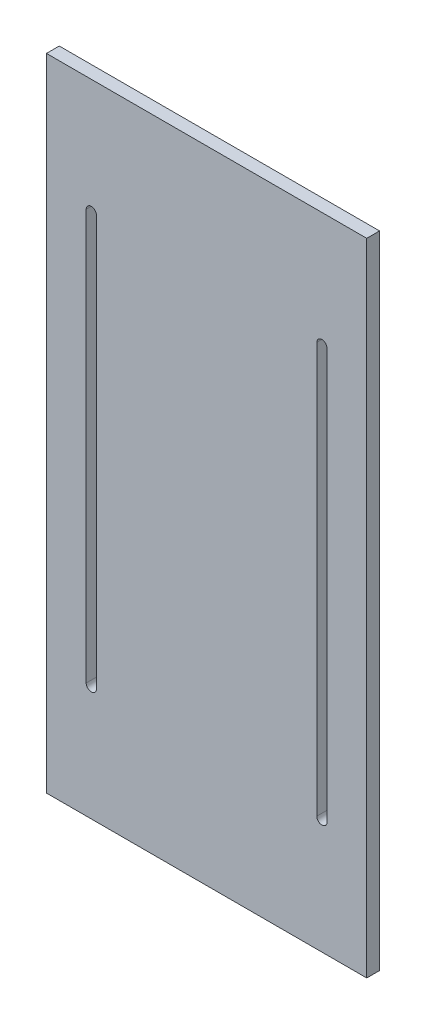
SolidWorks part; units mm, degrees
ref_plane "Front Plane" through (0, 0, 0) normal (0, 0, 1) x (1, 0, 0)
ref_plane "Top Plane" through (0, 0, 0) normal (0, 1, 0) x (1, 0, 0)
ref_plane "Right Plane" through (0, 0, 0) normal (1, 0, 0) x (0, 0, -1)
sketch "Sketch1" plane through (0, 0, 0) normal (0, 0, 1) x (1, 0, 0)
  line L1 (-25, -50) -> (25, -50)
  line L2 (-25, -50) -> (-25, 50)
  line L3 (-25, 50) -> (25, 50)
  line L4 (25, -50) -> (25, 50)
  line L5 (-25, -50) -> (25, 50) construction
  line L6 (-25, 50) -> (25, -50) construction
  point P0 (0, 0)
  dimension "D1" = 50
  dimension "D2" = 100
extrude "Boss-Extrude1" add sketch "Sketch1" along normal blind 2
sketch "Sketch2" plane through (0, 0, 0) normal (0, 0, -1) x (-1, 0, 0)
  line L0 (1.1, 0) -> (-1.1, 0) construction
  line L1 (-18.8, 0) -> (-17.2, 0)
  line L2 (-18.8, 0) -> (-18.8, 32.022)
  line L4 (-17.2, 0) -> (-17.2, 32.022)
  line L5 (0, 1.1) -> (0, -1.1) construction
  arc A0 (-18.8, 32.022) -> (-17.2, 32.022) centre (-18, 32.022) cw
  dimension "D2" = 0.8
  dimension "D1" = 18.8
extrude "Cut-Extrude1" cut sketch "Sketch2" against normal through all
pattern_linear "LPattern1" count 2 spacing 36 along (-1, 0, 0) of "Cut-Extrude1"
mirror "Mirror1" about plane through (0, 0, 0) normal (0, 1, 0) of "LPattern1"
